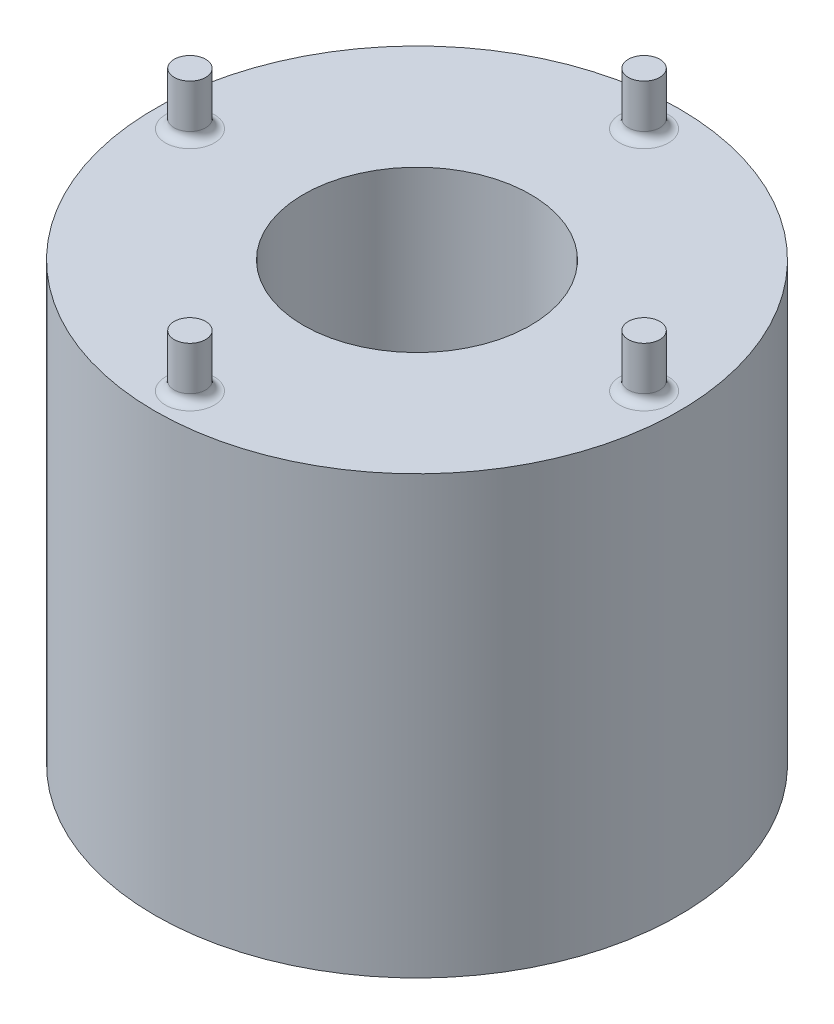
SolidWorks part; units mm, degrees
ref_plane "Front Plane" through (0, 0, 0) normal (0, 0, 1) x (1, 0, 0)
ref_plane "Top Plane" through (0, 0, 0) normal (0, 1, 0) x (1, 0, 0)
ref_plane "Right Plane" through (0, 0, 0) normal (1, 0, 0) x (0, 0, -1)
sketch "Sketch1" plane through (0, 0, 0) normal (0, 1, 0) x (1, 0, 0)
  circle A1 centre (0, 0) radius 15
  dimension "D2" = 30
extrude "Boss-Extrude1" add sketch "Sketch1" along normal blind 10 contours A1
sketch "Sketch2" plane through (0, 10, 0) normal (0, 1, 0) x (1, 0, 0)
  circle A0 centre (0, 0) radius 15
  circle A2 centre (0, 0) radius 15 construction
extrude "Boss-Extrude2" add sketch "Sketch2" along normal blind 15
sketch "Sketch3" plane through (0, 25, 0) normal (0, 1, 0) x (1, 0, 0)
  line L0 (0, -5.5) -> (0, 5.5) construction
  line L1 (-5.5, 0) -> (5.5, 0) construction
  circle A0 centre (0, -13) radius 0.9
  dimension "D1" = 1.8
  dimension "D2" = 13
extrude "Boss-Extrude3" add sketch "Sketch3" along normal blind 3
fillet "Fillet1" radius 0.5 1 edges at (0, 25, 13.9)
pattern_circular "CirPattern1" count 4 every 90 about axis through (0, 25, 0) along (0, 1, 0) of "Boss-Extrude3", "Fillet1"
sketch "Sketch5" plane through (0, 25, 0) normal (0, 1, 0) x (1, 0, 0)
  circle A0 centre (0, 0) radius 6.5
  dimension "D1" = 13
extrude "Cut-Extrude1" cut sketch "Sketch5" against normal blind 10
sketch "Sketch6" plane through (0, 15, 0) normal (0, 1, 0) x (1, 0, 0)
  circle A0 centre (0, 0) radius 1.75
  dimension "D1" = 3.5
extrude "Cut-Extrude2" cut sketch "Sketch6" against normal blind 10
fillet "Fillet2" radius 1 rebuild error yes
